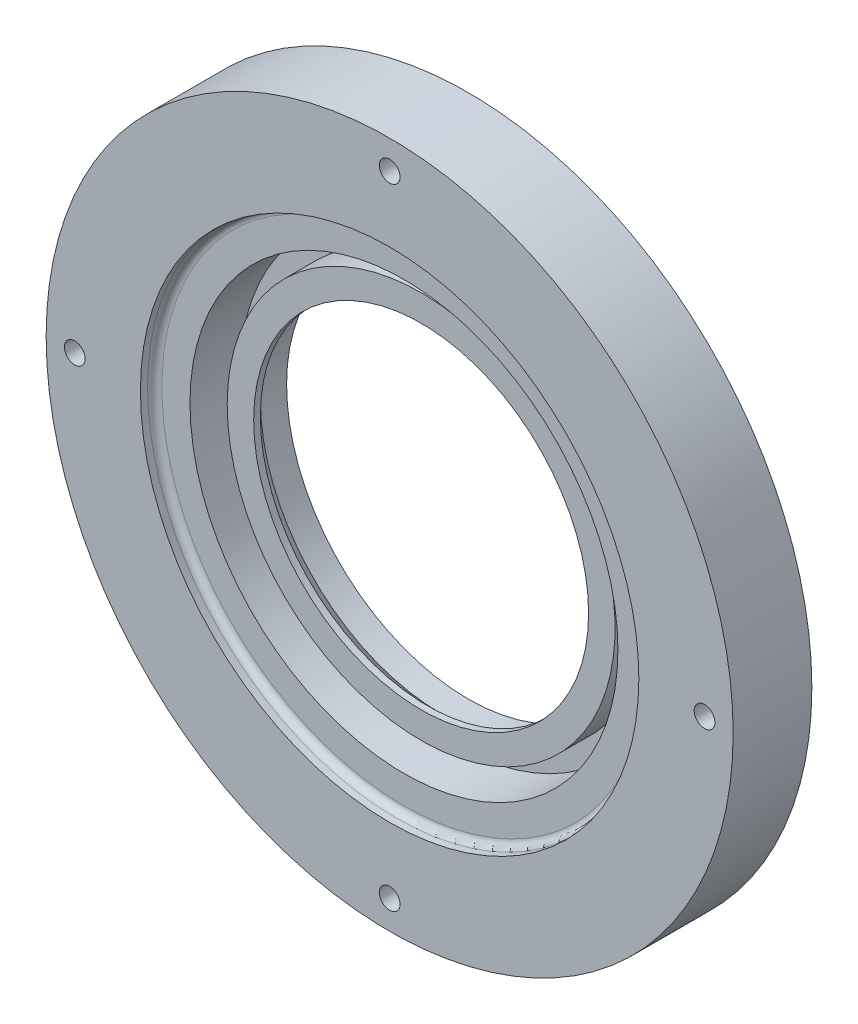
SolidWorks part; units mm, degrees
ref_plane "Front Plane" through (0, 0, 0) normal (0, 0, 1) x (1, 0, 0)
ref_plane "Top Plane" through (0, 0, 0) normal (0, 1, 0) x (1, 0, 0)
ref_plane "Right Plane" through (0, 0, 0) normal (1, 0, 0) x (0, 0, -1)
sketch "Sketch2" plane through (149.1164, 233.0393, -142.5293) normal (-0.6045, 0.7966, 0) x (0.7966, 0.6045, 0)
  line L0 (-23.4, 2.4) -> (-23.4, 3.3343)
  line L1 (-23.4, 3.3343) -> (-25.4, 5.3343)
  line L2 (-25.4, 5.3343) -> (-25.4, 9)
  line L3 (-25.4, 9) -> (-48, 9)
  line L17 (-27.1, 2.4) -> (-23.4, 2.4)
  line L18 (-34.825, 0) -> (-29.9, 0)
  line L19 (-23, 3.5) -> (-23, 2) construction
  line L20 (-29.9, 0) -> (-29.9, 7)
  line L21 (-29.5, 6.6) -> (-29.5, 0) construction
  line L25 (-25, 15) -> (-25, 5.5) construction
  line L26 (-25, 5.5) -> (-23, 3.5) construction
  line L27 (-27.1, 7) -> (-27.1, 2.4)
  line L28 (-27.5, 6.6) -> (-27.5, 2) construction
  line L30 (-27.1, 7) -> (-29.9, 7)
  line L32 (27.5, 2) -> (-27.5, 2) construction
  line L34 (29.5, 6.6) -> (-29.5, 6.6) construction
  line L36 (-29.5, 0) -> (29.5, 0) construction
  line L38 (-48, -2) -> (-34.825, -2)
  line L39 (-34.825, -2) -> (-34.825, 0)
  line L40 (-48, 9) -> (-48, -2)
  point P6 (-34.825, -1)
  dimension "D2" = 0.4
  dimension "D3" = 0.4
  dimension "D4" = 0.4
  dimension "D5" = 0.4
  dimension "D6" = 0.4
  dimension "D7" = 9
  dimension "D8" = 0.4
  dimension "D9" = 0.4
  dimension "D10" = 34.825
  dimension "D11" = 2
  dimension "D12" = 48
sketch "Sketch3" plane through (149.1164, 233.0393, -142.5293) normal (-0.6045, 0.7966, 0) x (0.7966, 0.6045, 0)
  line L0 (0, 13.4407) -> (0, -7.4209) construction
revolve "Revolve1" add sketch "Sketch2" angle 360 about L0
fillet "Fillet1" radius 1 1 edges at (114.2914, 233.0393, -142.5293)
hole_wizard "CBORE for M2.5 SHCS1" positions "Sketch10" profile "Sketch11" counterbore size "M2.5" standard "ANSI Metric"
sketch "Sketch10" plane through (0, 0, -151.5293) normal (0, 0, -1) x (-1, 0, 0)
  point P0 (-149.1164, 277.0393)
  point P2 (-149.1164, 189.0393)
  point P4 (-105.1164, 233.0393)
  point P6 (-193.1164, 233.0393)
  dimension "D1" = 44
  dimension "D2" = 44
  dimension "D3" = 88
  dimension "D4" = 88
sketch "Sketch11" plane through (149.1164, 277.0393, -151.5293) normal (1, 0, 0) x (0, 1, 0)
  line L0 (0, 0) -> (0, 11.8712)
  line L1 (0, 11.8712) -> (1.45, 11)
  line L2 (1.45, 11) -> (1.45, 5.5)
  line L3 (1.45, 5.5) -> (2.75, 5.5)
  line L4 (2.75, 5.5) -> (2.75, 0)
  line L5 (2.75, 0) -> (0, 0)
  line L10 (0, 11.8712) -> (-1.45, 11) construction
  line L11 (0, -6.35) -> (0, 107.95) construction
  dimension "Hole Dia." = 2.9
  dimension "Hole Depth" = 11
  dimension "C'Bore Dia." = 5.5
  dimension "C'Bore Depth" = 5.5
  dimension "Drill Angle" = 118
